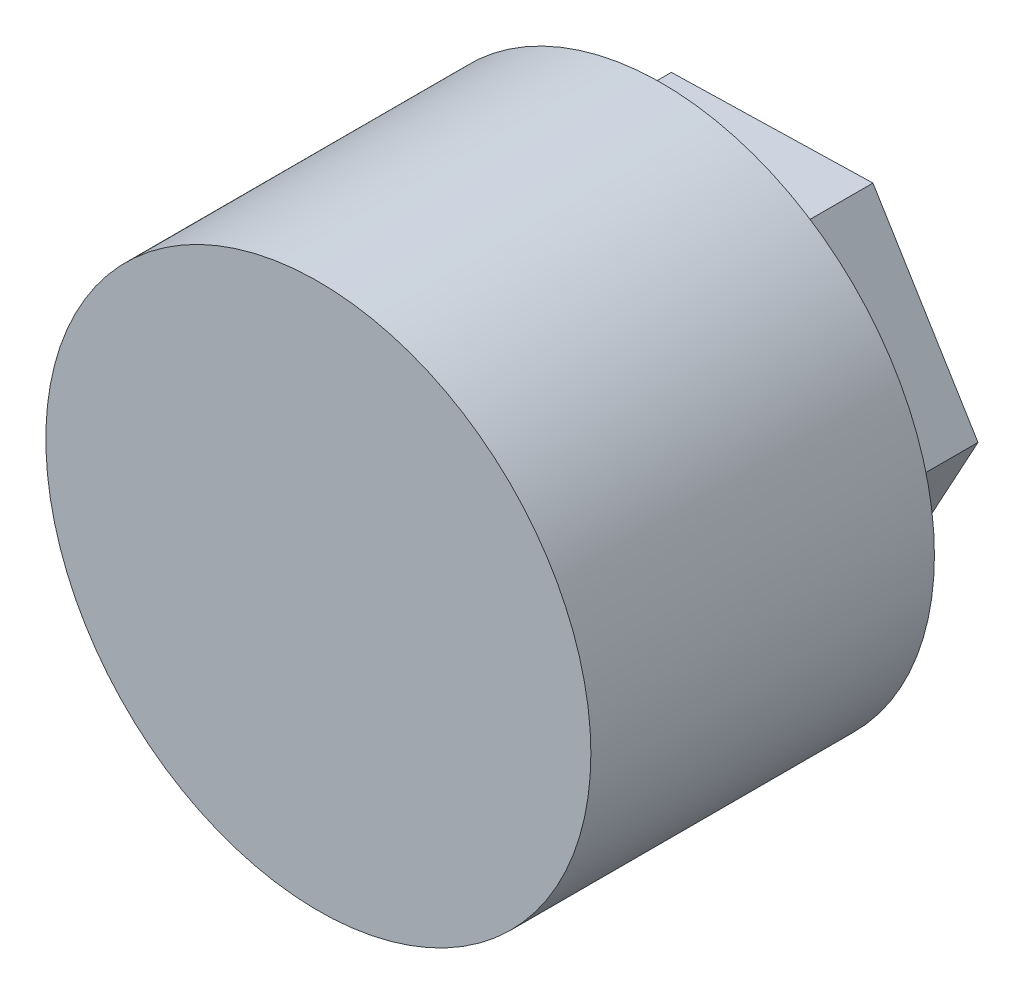
SolidWorks part; units mm, degrees
ref_plane "Спереди" through (0, 0, 0) normal (0, 0, 1) x (1, 0, 0)
ref_plane "Сверху" through (0, 0, 0) normal (0, 1, 0) x (1, 0, 0)
ref_plane "Справа" through (0, 0, 0) normal (1, 0, 0) x (0, 0, -1)
sketch "Эскиз1" plane through (0, 0, 0) normal (0, 0, 1) x (1, 0, 0)
  circle A0 centre (0, 0) radius 23.7976
extrude "Бобышка-Вытянуть1" add sketch "Эскиз1" along normal blind 30
sketch "Эскиз2" plane through (0, 0, 0) normal (0, 0, -1) x (-1, 0, 0)
  line L1 (8.4286, -15.4592) -> (17.6023, -0.4302)
  line L2 (17.6023, -0.4302) -> (9.1737, 15.029)
  line L3 (9.1737, 15.029) -> (-8.4286, 15.4592)
  line L4 (-8.4286, 15.4592) -> (-17.6023, 0.4302)
  line L5 (-17.6023, 0.4302) -> (-9.1737, -15.029)
  line L6 (-9.1737, -15.029) -> (8.4286, -15.4592)
  circle A0 centre (0, 0) radius 15.2486 construction
extrude "Бобышка-Вытянуть2" add sketch "Эскиз2" along normal blind 10
